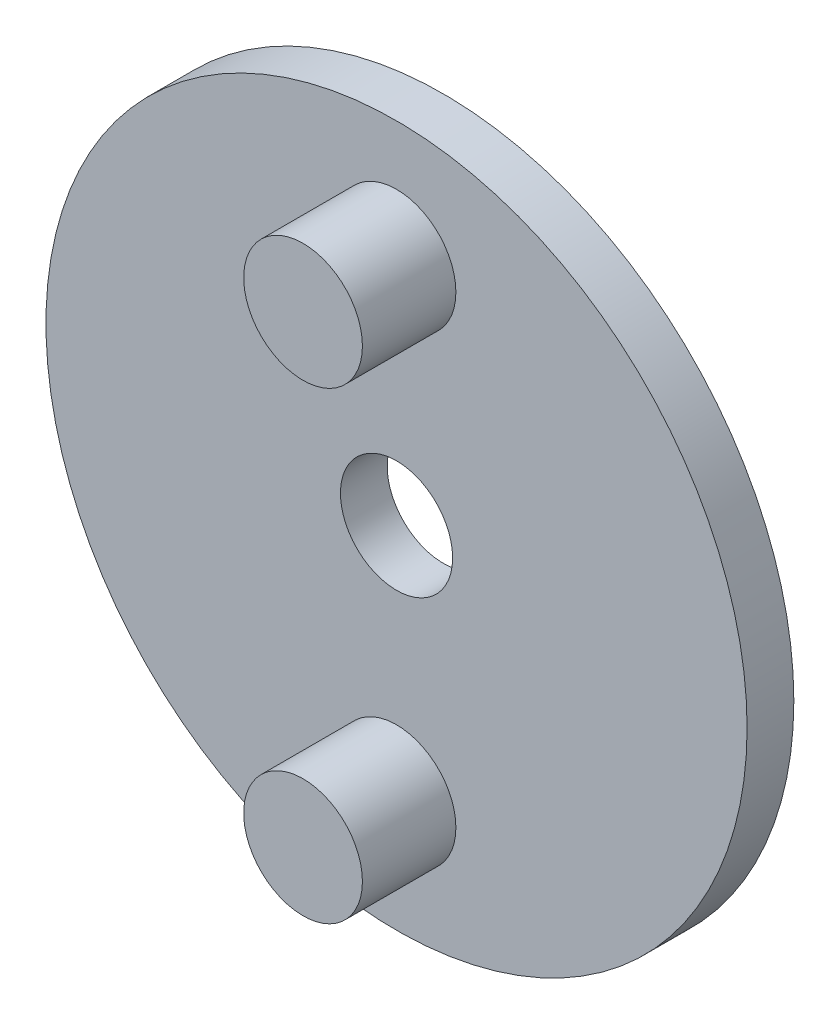
SolidWorks part; units mm, degrees
ref_plane "Front Plane" through (0, 0, 0) normal (0, 0, 1) x (1, 0, 0)
ref_plane "Top Plane" through (0, 0, 0) normal (0, 1, 0) x (1, 0, 0)
ref_plane "Right Plane" through (0, 0, 0) normal (1, 0, 0) x (0, 0, -1)
sketch "Sketch1" plane through (0, 0, 0) normal (0, 0, 1) x (1, 0, 0)
  line L0 (-169.7289, -37.5) -> (169.7289, -37.5) construction
  line L1 (-110.0162, 37.5) -> (110.0162, 37.5) construction
  circle A0 centre (0, 0) radius 37.5
  circle A1 centre (0, 0) radius 6
  circle A2 centre (0, -24.8) radius 6.35
  circle A3 centre (0, 24.8) radius 6.35
  point P7 (0, -37.5)
  point P14 (0, 37.5)
  point P15 (110.0162, 75.6194)
  dimension "D1" = 75
  dimension "D2" = 12.7
  dimension "D3" = 12
  dimension "D5" = 12.7
  dimension "D4" = 12.7
  dimension "D6" = 12.7
extrude "Boss-Extrude1" add sketch "Sketch1" along normal blind 5
sketch "Sketch2" plane through (0, 0, 0) normal (0, 0, 1) x (1, 0, 0)
  circle A0 centre (0, -24.8) radius 6.35
  circle A1 centre (0, 24.8) radius 6.35
  circle A3 centre (0, 24.8) radius 6.35 construction
extrude "Boss-Extrude2" add sketch "Sketch2" along normal blind 15
